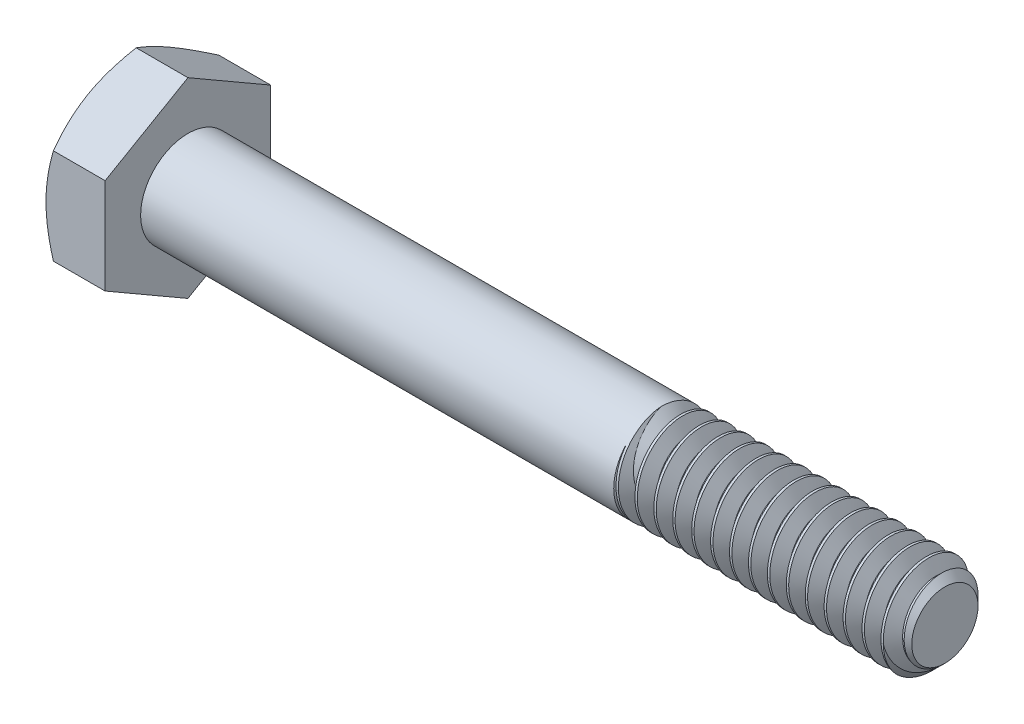
SolidWorks part; units mm, degrees
ref_plane "Front Plane" through (0, 0, 0) normal (0, 0, 1) x (1, 0, 0)
ref_plane "Top Plane" through (0, 0, 0) normal (0, 1, 0) x (1, 0, 0)
ref_plane "Right Plane" through (0, 0, 0) normal (1, 0, 0) x (0, 0, -1)
sketch "Sketch1" plane through (0, 0, 0) normal (0, 0, 1) x (1, 0, 0)
  line L0 (-27.3844, 0) -> (27.3844, 0) construction
  line L1 (27.3844, 3.175) -> (27.3844, -3.175) construction
  line L2 (-23.4156, 5.5562) -> (-23.4156, -5.5562) construction
  line L3 (-27.3844, 5.5562) -> (-27.3844, -5.5562) construction
  point P9 (-23.4156, 0)
  point P10 (22.9394, -3.175)
  dimension "Screw Dia" = 6.35
  dimension "Hex" = 11.1125
  dimension "Head Ht" = 3.9688
  dimension "Screw Lenght" = 50.8
  dimension "D1" = 4.445
ref_plane "Plane2" through (27.3844, 0, 0) normal (1, 0, 0) x (0, 0, -1)
sketch "Sketch5" plane through (27.3844, 0, 0) normal (1, 0, 0) x (0, 0, -1)
  circle A0 centre (0, 0) radius 3.175
extrude "Boss-Extrude3" add sketch "Sketch5" against normal up to vertex (50.8 mm away) up to point (-23.4156, 0, 0)
sketch "Sketch9" plane through (27.3844, 0, 0) normal (1, 0, 0) x (0, 0, -1)
  circle A1 centre (0, 0) radius 3.175
  circle A2 centre (0, 0) radius 3.175
  dimension "D1" = 0
curve "Helix/Spiral1" pitch 1.27 height 20.32 turns 16 parameters "Pitch"=1.27
chamfer "Chamfer1" distance 0.9525 angle 45 1 edges at (27.3844, 0, -3.175)
sketch "Sketch10" plane through (0, 0, 0) normal (0, 0, 1) x (1, 0, 0)
  line L0 (27.3844, 3.175) -> (27.8606, 2.3501)
  line L1 (27.8606, 2.3501) -> (28.0194, 2.3501)
  line L2 (28.0194, 2.3501) -> (28.4956, 3.175)
  line L3 (27.3844, 3.175) -> (28.4956, 3.175)
  line L4 (27.94, 3.175) -> (27.94, 2.3501) construction
  line L5 (27.6225, 2.7626) -> (28.2575, 2.7626) construction
  dimension "D1" = 60
  dimension "D2" = 0.1588
  dimension "D3" = 0.635
sweep "Cut-Sweep1" cut profiles "Sketch10" path "Helix/Spiral1" align with end faces yes
sketch "Sketch11" plane through (0, 0, 0) normal (0, 0, 1) x (1, 0, 0)
  line L0 (-23.4156, 3.175) -> (-23.4156, 0)
  line L1 (-23.4156, 0) -> (11.5094, 0)
  line L3 (11.5094, 0) -> (8.3344, 3.175)
  line L4 (-23.4156, 3.175) -> (8.3344, 3.175)
  dimension "D1" = 45
  dimension "MIn Thread" = 19.05
revolve "Revolve1" add sketch "Sketch11" angle 360 about L1
sketch "Sketch6" plane through (-23.4156, 0, 0) normal (-1, 0, 0) x (0, 0, 1)
  line L0 (0, 5.5562) -> (0, -5.5562) construction
  line L1 (5.5562, 3.2079) -> (0, 6.4158)
  line L2 (0, 6.4158) -> (-5.5562, 3.2079)
  line L3 (-5.5562, 3.2079) -> (-5.5562, -3.2079)
  line L4 (-5.5562, -3.2079) -> (0, -6.4158)
  line L5 (0, -6.4158) -> (5.5562, -3.2079)
  line L6 (5.5562, -3.2079) -> (5.5562, 3.2079)
  circle A0 centre (0, 0) radius 5.5562 construction
extrude "Boss-Extrude4" add sketch "Sketch6" along normal up to vertex (3.9688 mm away) up to point (-27.3844, -5.5562, 0)
sketch "Sketch7" plane through (-27.3844, 0, 0) normal (-1, 0, 0) x (0, 0, 1)
  circle A0 centre (0, 0) radius 5.5562 construction
  circle A1 centre (0, 0) radius 5.5562
sketch "Sketch8" plane through (-27.3844, 0, 0) normal (-1, 0, 0) x (0, 0, 1)
  circle A0 centre (0, 0) radius 5.5562 construction
  circle A1 centre (0, 0) radius 5.5562
extrude "Cut-Extrude3" cut sketch "Sketch8" against normal through all draft 60 flip side to cut
equation "\"D2@Sketch10\" = \"Pitch@Helix/Spiral1\"*.125"
equation "\"D3@Sketch10\" = \"Pitch@Helix/Spiral1\"*.5"
equation "\"D3@Helix/Spiral1\" = \"MIn Thread@Sketch11\"+\"Pitch@Helix/Spiral1\""
equation "\"D1@Chamfer1\" = \"Pitch@Helix/Spiral1\"*.75"
equation "\"D1@Sketch1\" = \"Pitch@Helix/Spiral1\"*3.5"
